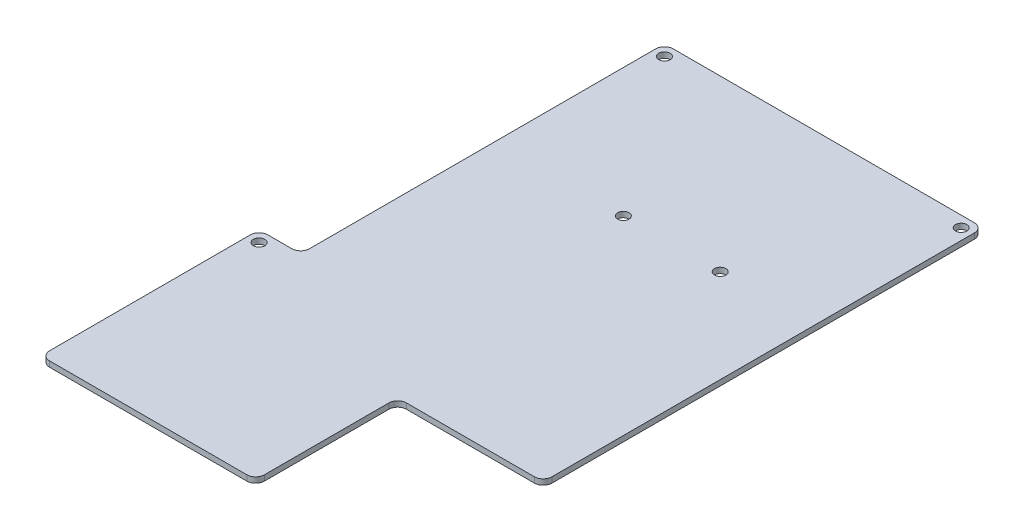
SolidWorks part; units mm, degrees
ref_plane "Front" through (0, 0, 0) normal (0, 0, 1) x (1, 0, 0)
ref_plane "Top" through (0, 0, 0) normal (0, 1, 0) x (1, 0, 0)
ref_plane "Right" through (0, 0, 0) normal (1, 0, 0) x (0, 0, -1)
sketch "Sketch1" plane through (0, 0, 0) normal (0, 1, 0) x (1, 0, 0)
  line L1 (-46, -63.5) -> (46, -63.5)
  line L2 (-46, -63.5) -> (-46, 63.5)
  line L3 (-46, 63.5) -> (46, 63.5)
  line L4 (46, -63.5) -> (46, 63.5)
  line L5 (-46, -63.5) -> (46, 63.5) construction
  line L6 (-46, 63.5) -> (46, -63.5) construction
  point P0 (0, 0)
  dimension "D1" = 127
  dimension "D2" = 92
extrude "Boss-Extrude1" add sketch "Sketch1" along normal blind 1.6
hole_wizard "#4 Clearance Hole1" positions "Sketch4" profile "Sketch5" hole size "#4" standard "ANSI Inch"
sketch "Sketch4" plane through (0, 1.6, 0) normal (0, 1, 0) x (1, 0, 0)
  line L1 (46, -63.5) -> (46, 63.5) construction
  line L2 (46, 63.5) -> (-46, 63.5) construction
  line L3 (-46, 63.5) -> (-46, -63.5) construction
  point P22 (19.05, 14.54)
  point P24 (-8.89, 14.54)
  dimension "D1" = 26.95
  dimension "D2" = 48.96
  dimension "D3" = 48.96
  dimension "D4" = 37.11
sketch "Sketch5" plane through (19.05, 1.6, -14.54) normal (1, 0, 0) x (0, 0, 1)
  line L0 (0, 0) -> (0, 19.7306)
  line L1 (0, 19.7306) -> (1.6319, 18.75)
  line L2 (1.6319, 18.75) -> (1.6319, 0)
  line L5 (1.6319, 0) -> (0, 0)
  line L10 (0, 19.7306) -> (-1.632, 18.75) construction
  line L11 (0, -6.35) -> (0, 107.95) construction
  dimension "Hole Dia." = 3.2639
  dimension "Hole Depth" = 18.75
  dimension "Drill Angle" = 118
hole_wizard "#8 Clearance Hole1" positions "Sketch6" profile "Sketch7" hole size "#8" standard "ANSI Inch"
sketch "Sketch6" plane through (0, 0, 0) normal (0, -1, 0) x (-1, 0, 0)
  circle A0 centre (22.07, -45.25) radius 1.5 construction
  point P0 (22.07, -45.25)
sketch "Sketch7" plane through (-22.07, 0, 45.25) normal (1, 0, 0) x (0, 0, -1)
  line L0 (0, 0) -> (0, 20.1007)
  line L1 (0, 20.1007) -> (2.2479, 18.75)
  line L2 (2.2479, 18.75) -> (2.2479, 0)
  line L5 (2.2479, 0) -> (0, 0)
  line L10 (0, 20.1007) -> (-2.2479, 18.75) construction
  line L11 (0, -6.35) -> (0, 107.95) construction
  dimension "Hole Dia." = 4.4958
  dimension "Hole Depth" = 18.75
  dimension "Drill Angle" = 118
sketch "Sketch8" plane through (0, 0, 0) normal (0, 1, 0) x (1, 0, 0)
  line L0 (-46, -63.5) -> (46, -63.5) construction
  line L1 (4, -41.5) -> (-58, -41.5)
  line L2 (4, -41.5) -> (4, -104.5)
  line L3 (4, -104.5) -> (-58, -104.5)
  line L4 (-58, -41.5) -> (-58, -104.5)
  line L5 (4, -41.5) -> (-58, -104.5) construction
  line L6 (4, -104.5) -> (-58, -41.5) construction
  line L7 (-46, 63.5) -> (-46, -63.5) construction
  point P0 (-27, -73)
  dimension "D1" = 22
  dimension "D2" = 50
  dimension "D3" = 62
  dimension "D4" = 63
extrude "Boss-Extrude2" add sketch "Sketch8" along normal blind 1.6
hole_wizard "#4 Clearance Hole2" positions "Sketch2" profile "Sketch3" hole size "#4" standard "ANSI Inch"
sketch "Sketch2" plane through (0, 1.6, 0) normal (0, 1, 0) x (1, 0, 0)
  line L1 (-42.825, 60.325) -> (42.825, 60.325)
  line L2 (-42.825, 60.325) -> (-42.825, -60.325)
  line L3 (-42.825, -60.325) -> (42.825, -60.325)
  line L4 (42.825, 60.325) -> (42.825, -60.325)
  line L5 (-42.825, 60.325) -> (42.825, -60.325) construction
  line L6 (-42.825, -60.325) -> (42.825, 60.325) construction
  line L9 (46, -63.5) -> (46, 63.5) construction
  line L10 (4, -63.5) -> (46, -63.5) construction
  line L11 (-46, -41.5) -> (-58, -41.5) construction
  line L12 (-58, -41.5) -> (-58, -104.5) construction
  point P0 (-42.825, 60.325)
  point P2 (42.825, 60.325)
  point P118 (-54.82, -44.68)
  dimension "D1" = 3.175
  dimension "D2" = 3.175
  dimension "D3" = 3.18
  dimension "D4" = 3.18
sketch "Sketch3" plane through (-42.825, 1.6, -60.325) normal (1, 0, 0) x (0, 0, 1)
  line L0 (0, 0) -> (0, 50.9806)
  line L1 (0, 50.9806) -> (1.6319, 50)
  line L2 (1.6319, 50) -> (1.6319, 0)
  line L5 (1.6319, 0) -> (0, 0)
  line L10 (0, 50.9806) -> (-1.632, 50) construction
  line L11 (0, -6.35) -> (0, 107.95) construction
  dimension "Hole Dia." = 3.2639
  dimension "Hole Depth" = 50
  dimension "Drill Angle" = 118
fillet "Fillet1" radius 2.54 8 edges at (46, 0.8, 63.5) (46, 0.8, -63.5) (-46, 0.8, -63.5) (4, 0.8, 63.5) (4, 0.8, 104.5) (-58, 0.8, 104.5) (-58, 0.8, 41.5) (-46, 0.8, 41.5)
ref_point "PCB_ORIGIN"
sketch "TOP_KEEPOUT" plane through (0, 1.6, 0) normal (0, 1, 0) x (1, 0, 0)
  circle A0 centre (-8.89, 14.54) radius 3.429
  circle A1 centre (19.05, 14.54) radius 3.429
  circle A2 centre (42.825, 60.325) radius 3.429
  circle A3 centre (-42.825, 60.325) radius 3.429
  circle A6 centre (-54.82, -44.68) radius 3.429
  dimension "D1" = 6.858
sketch "BOTTOM_KEEPOUT" plane through (0, 0, 0) normal (0, -1, 0) x (1, 0, 0)
  line L0 (-26.67, -46.036) -> (-26.67, -3.11) construction
  line L1 (26.67, -47.56) -> (-26.67, -47.56)
  line L2 (26.67, -47.56) -> (26.67, 51.5)
  line L3 (26.67, 51.5) -> (-21.67, 51.5)
  line L4 (-26.67, -47.56) -> (-26.67, 41.5)
  line L7 (-13.716, -47.56) -> (-25.146, -47.56) construction
  line L9 (26.67, -3.11) -> (26.67, -46.56) construction
  line L10 (-25.67, 51.5) -> (25.67, 51.5) construction
  line L11 (-21.67, 51.5) -> (-21.67, 41.5)
  line L12 (-21.67, 41.5) -> (-26.67, 41.5)
  circle A2 centre (42.825, -60.325) radius 3.937
  circle A3 centre (-42.825, -60.325) radius 3.937
  circle A4 centre (-54.82, 44.68) radius 3.937
  dimension "D1" = 7.874
  dimension "D4" = 5
  dimension "D5" = 10
sketch "TOP_CONN_POS" plane through (0, 1.6, 0) normal (0, 1, 0) x (1, 0, 0)
  line L0 (6.35, -35.308) -> (6.35, -45.308)
  line L1 (-37.936, 28.7076) -> (-37.936, 18.7076)
  line L2 (1.35, -40.308) -> (11.35, -40.308)
  line L3 (-42.936, 23.7076) -> (-32.936, 23.7076)
  line L4 (0, 60.436) -> (0, 50.436)
  line L5 (-5, 55.436) -> (5, 55.436)
  line L6 (-37.936, -5.35) -> (-37.936, 52.7652) construction
  line L7 (-43.524, 23.7076) -> (-32.348, 23.7076) construction
  line L8 (0, 61.024) -> (0, 49.848) construction
  line L9 (-29.0576, 55.436) -> (29.0576, 55.436) construction
  line L10 (37.936, 28.7076) -> (37.936, 18.7076)
  line L11 (32.936, 23.7076) -> (42.936, 23.7076)
  line L12 (43.524, 23.7076) -> (32.348, 23.7076) construction
  line L13 (37.936, 52.7652) -> (37.936, -5.35) construction
  line L14 (37.936, -25.0576) -> (37.936, -35.0576)
  line L15 (32.936, -30.0576) -> (42.936, -30.0576)
  line L16 (37.936, -52.7652) -> (37.936, -7.35) construction
  line L17 (43.524, -30.0576) -> (32.348, -30.0576) construction
  line L18 (0, -50.436) -> (0, -60.436)
  line L19 (-5, -55.436) -> (5, -55.436)
  line L20 (29.0576, -55.436) -> (-29.0576, -55.436) construction
  line L21 (0, -61.024) -> (0, -49.848) construction
  line L22 (6.35, -45.896) -> (6.35, -34.72) construction
  line L23 (-16.3576, -40.308) -> (29.0576, -40.308) construction
  line L24 (-41.4, -10.83) -> (-41.4, -20.83)
  line L25 (-46.4, -15.83) -> (-36.4, -15.83)
  line L26 (-41.4, -36.98) -> (-41.4, -26.98)
  line L27 (-46.4, -31.98) -> (-36.4, -31.98)
  line L28 (-0.6, -90.425) -> (-0.6, -100.425)
  line L29 (-5.6, -95.425) -> (4.4, -95.425)
  line L30 (4, -95.425) -> (-11.4, -95.425) construction
  line L31 (-0.6, -100.75) -> (-0.6, -90.1) construction
  line L32 (-41.4, -25.155) -> (-41.4, -38.805) construction
  line L33 (-46, -31.98) -> (-30.92, -31.98) construction
  line L34 (-46, -15.83) -> (-30.92, -15.83) construction
  line L35 (-41.4, -9.005) -> (-41.4, -22.655) construction
  point P2 (6.35, -40.308)
  point P9 (-37.936, 23.7076)
  point P14 (0, 55.436)
  point P17 (-41.4, -15.83)
  point P29 (37.936, 23.7076)
  point P40 (37.936, -30.0576)
  point P50 (0, -55.436)
  point P53 (-41.4, -31.98)
  point P66 (-0.6, -95.425)
  dimension "D1" = 10
  dimension "D2" = 0
  dimension "D3" = 0
  dimension "D4" = 0
  dimension "D5" = 0
  dimension "D6" = 0
  dimension "D7" = 0
  dimension "D8" = 0
  dimension "D9" = 0
  dimension "D10" = 0
  dimension "D11" = 0
  dimension "D12" = 0
  dimension "D13" = 0
  dimension "D14" = 0
  dimension "D15" = 0
  dimension "D16" = 0
  dimension "D17" = 0
  dimension "D18" = 0
  dimension "D19" = 0
sketch "BOTTOM_CONN_POS" plane through (0, 1.6, 0) normal (0, 1, 0) x (1, 0, 0)
  line L0 (0, 12.768) -> (0, -17.232)
  line L1 (-15, -2.232) -> (15, -2.232)
  line L2 (-41.4, 47.27) -> (-41.4, 37.27)
  line L3 (-46.4, 42.27) -> (-36.4, 42.27)
  line L4 (-46, 42.27) -> (-30.6, 42.27) construction
  line L5 (-41.4, 50.595) -> (-41.4, 33.945) construction
  line L6 (-41.4, 28.62) -> (-41.4, 18.62)
  line L7 (-46.4, 23.62) -> (-36.4, 23.62)
  line L8 (-41.4, 12.97) -> (-41.4, 2.97)
  line L9 (-46.4, 7.97) -> (-36.4, 7.97)
  line L10 (-41.4, 0.32) -> (-41.4, -9.68)
  line L11 (-46.4, -4.68) -> (-36.4, -4.68)
  line L12 (-41.4, -12.33) -> (-41.4, -22.33)
  line L13 (-46.4, -17.33) -> (-36.4, -17.33)
  line L14 (-46, 23.62) -> (-30.6, 23.62) construction
  line L15 (-46, 7.97) -> (-30.6, 7.97) construction
  line L16 (-46, -4.68) -> (-30.6, -4.68) construction
  line L17 (-46, -17.33) -> (-30.6, -17.33) construction
  line L18 (-39, -24.955) -> (-39, -34.955)
  line L19 (-44, -29.955) -> (-34, -29.955)
  line L32 (-39, -34.655) -> (-39, -25.255) construction
  line L33 (-42.65, -29.955) -> (-35.5, -29.955) construction
  line L40 (39.35, -41.555) -> (39.35, -51.555)
  line L41 (34.35, -46.555) -> (44.35, -46.555)
  line L42 (41.4, -9.33) -> (41.4, -19.33)
  line L43 (36.4, -14.33) -> (46.4, -14.33)
  line L44 (39.35, -24.455) -> (39.35, -34.455)
  line L45 (34.35, -29.455) -> (44.35, -29.455)
  line L46 (39.35, -39.355) -> (39.35, -53.755) construction
  line L47 (35.85, -46.555) -> (43, -46.555) construction
  line L48 (35.85, -29.455) -> (43, -29.455) construction
  line L49 (41.4, -9.005) -> (41.4, -19.655) construction
  line L50 (46, -14.33) -> (30.6, -14.33) construction
  line L51 (41.4, 3.32) -> (41.4, -6.68)
  line L52 (36.4, -1.68) -> (46.4, -1.68)
  line L53 (41.4, 17.47) -> (41.4, 7.47)
  line L54 (36.4, 12.47) -> (46.4, 12.47)
  line L61 (46, -1.68) -> (30.6, -1.68) construction
  line L62 (46, 12.47) -> (30.92, 12.47) construction
  line L63 (41.4, 33.12) -> (41.4, 23.12)
  line L64 (36.4, 28.12) -> (46.4, 28.12)
  line L65 (46, 28.12) -> (30.92, 28.12) construction
  line L66 (41.4, 48.77) -> (41.4, 38.77)
  line L67 (36.4, 43.77) -> (46.4, 43.77)
  line L68 (46, 43.77) -> (30.92, 43.77) construction
  line L69 (27.975, 63.9) -> (27.975, 53.9)
  line L70 (22.975, 58.9) -> (32.975, 58.9)
  line L71 (21.15, 58.9) -> (34.8, 58.9) construction
  line L72 (27.975, 63.5) -> (27.975, 48.42) construction
  line L73 (10.825, 63.9) -> (10.825, 53.9)
  line L74 (5.825, 58.9) -> (15.825, 58.9)
  line L75 (10.825, 63.5) -> (10.825, 48.1) construction
  line L76 (-7.825, 63.9) -> (-7.825, 53.9)
  line L77 (-12.825, 58.9) -> (-2.825, 58.9)
  line L78 (-7.825, 63.5) -> (-7.825, 48.1) construction
  line L79 (-26.475, 63.9) -> (-26.475, 53.9)
  line L80 (-31.475, 58.9) -> (-21.475, 58.9)
  line L81 (-26.475, 63.5) -> (-26.475, 48.1) construction
  line L82 (0, -51.5) -> (0, 50.1) construction
  line L83 (26.67, -2.232) -> (-26.67, -2.232) construction
  point P4 (0, -2.232)
  point P5 (0, 0)
  point P13 (-41.4, 42.27)
  point P24 (-41.4, 23.62)
  point P29 (-41.4, 7.97)
  point P34 (-41.4, -4.68)
  point P39 (-41.4, -17.33)
  point P56 (-39, -29.955)
  point P105 (39.35, -46.555)
  point P110 (41.4, -14.33)
  point P115 (39.35, -29.455)
  point P135 (41.4, -1.68)
  point P140 (41.4, 12.47)
  point P151 (41.4, 28.12)
  point P161 (41.4, 43.77)
  point P169 (27.975, 58.9)
  point P179 (10.825, 58.9)
  point P188 (-7.825, 58.9)
  point P197 (-26.475, 58.9)
  dimension "D1" = 30
  dimension "D2" = 10
  dimension "D3" = 0
  dimension "D4" = 0
  dimension "D5" = 10
  dimension "D6" = 10
  dimension "D7" = 10
  dimension "D8" = 10
  dimension "D9" = 0
  dimension "D10" = 0
  dimension "D11" = 0
  dimension "D12" = 0
  dimension "D13" = 10
  dimension "D16" = 0
  dimension "D17" = 0
  dimension "D24" = 0
  dimension "D25" = 0
  dimension "D26" = 0
  dimension "D27" = 0
  dimension "D28" = 0
  dimension "D29" = 10
  dimension "D30" = 10
  dimension "D31" = 0
  dimension "D32" = 0
  dimension "D33" = 10
  dimension "D34" = 0
  dimension "D35" = 10
  dimension "D36" = 0
  dimension "D37" = 10
  dimension "D38" = 0
  dimension "D39" = 0
  dimension "D40" = 10
  dimension "D41" = 0
  dimension "D42" = 10
  dimension "D43" = 0
  dimension "D44" = 10
  dimension "D45" = 0
  dimension "D46" = 0
  dimension "D47" = 0
